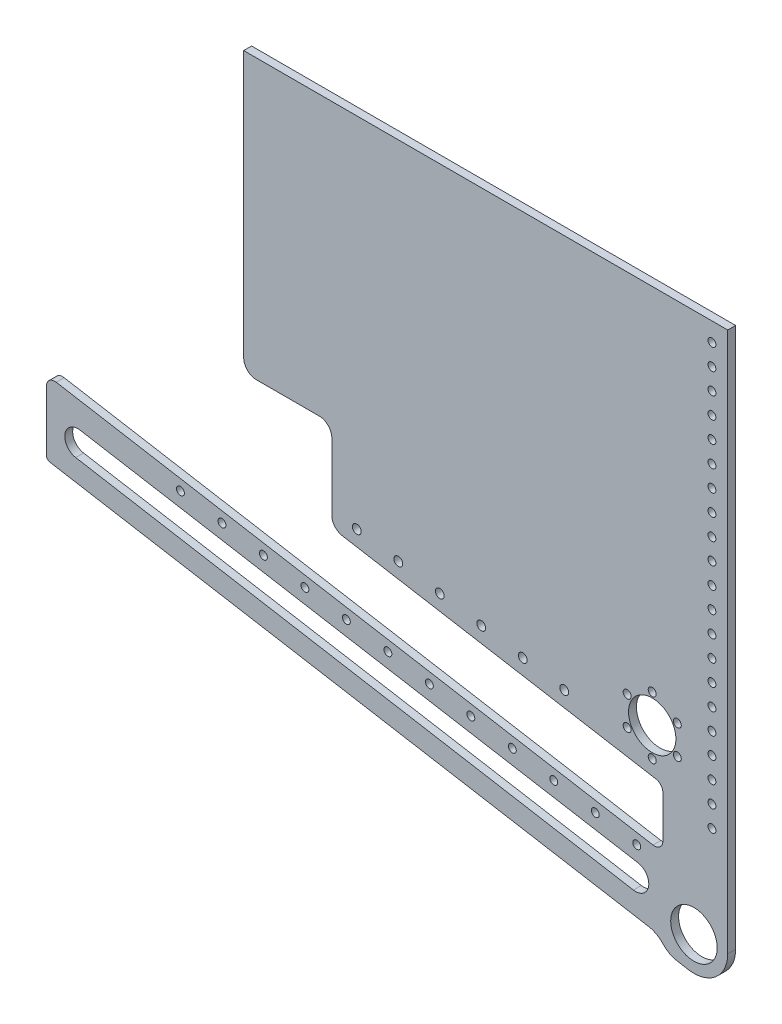
SolidWorks part; units mm, degrees
material "Polypropylene"
ref_plane "Front Plane" through (0, 0, 0) normal (0, 0, 1) x (1, 0, 0)
ref_plane "Top Plane" through (0, 0, 0) normal (0, 1, 0) x (1, 0, 0)
ref_plane "Right Plane" through (0, 0, 0) normal (1, 0, 0) x (0, 0, -1)
sketch "Sketch1" plane through (0, 0, 0) normal (0, 0, 1) x (1, 0, 0)
  line L0 (19.05, 0) -> (19.05, -76.2) construction
  line L1 (0, 19.05) -> (-57.15, 19.05) construction
  line L2 (19.05, -155.575) -> (168.9894, -155.575) construction
  line L3 (0, -95.25) -> (-57.15, -95.25) construction
  line L4 (-57.15, -95.25) -> (-57.15, 19.05) construction
  line L5 (168.9894, 7.239) -> (168.9894, -18.161) construction
  line L6 (168.9894, -18.161) -> (168.9894, -155.575) construction
  line L7 (168.9894, 7.239) -> (143.6189, 6.0141) construction
  line L8 (143.6189, 6.0141) -> (19.05, 0) construction
  line L9 (165.5424, -12.8509) -> (158.8645, -11.7052)
  line L10 (189.3729, 7.239) -> (189.3729, 131.5601)
  line L12 (197.5644, 110.4886) -> (197.5644, -33.1911) construction
  line L16 (-221.8076, 98.3842) -> (-221.8076, 62.1942)
  line L17 (133.7924, 19.9786) -> (-202.7576, 77.7234) construction
  line L18 (132.4501, 12.1554) -> (-204.0999, 69.9002)
  line L19 (135.1346, 27.8017) -> (-201.4154, 85.5465)
  line L20 (-215.8686, 103.3911) -> (107.3768, 47.929)
  line L23 (-219.6972, 59.6908) -> (141.5847, -2.2975)
  line L24 (179.8479, 131.5601) -> (179.8479, 118.8601) construction
  line L25 (179.8479, 118.8601) -> (189.3729, 118.8601) construction
  line L31 (107.3768, 47.929) -> (144.2855, 41.5963)
  line L32 (150.2246, 46.6031) -> (150.2246, 72.0031)
  line L38 (146.0036, 77.01) -> (-43.2183, 109.4764)
  line L40 (189.3729, 131.5601) -> (189.3729, 333.3075)
  line L42 (-102.7271, 172.6972) -> (-102.7271, 333.3075)
  line L43 (-102.7271, 333.3075) -> (189.3729, 333.3075)
  line L48 (-49.5497, 116.9867) -> (-49.5497, 157.4572)
  line L49 (-57.1697, 165.0772) -> (-95.1071, 165.0772)
  line L50 (-40.7554, 66.9026) -> (-34.4671, 117.3119) construction
  line L51 (34.3472, 54.0166) -> (40.7189, 104.4154) construction
  line L52 (-34.4671, 117.3119) -> (40.7189, 104.4154) construction
  arc A0 (19.05, 0) -> (0, 19.05) centre (0, 0) ccw construction
  arc A1 (19.05, -76.2) -> (0, -95.25) centre (0, -76.2) cw construction
  circle A2 centre (168.9894, 7.239) radius 14.0335
  arc A3 (168.9894, -18.161) -> (143.6189, 6.0141) centre (168.9894, 7.239) ccw construction
  arc A4 (165.5424, -12.8509) -> (189.3729, 7.239) centre (168.9894, 7.239) ccw
  arc A5 (132.4501, 12.1554) -> (135.1346, 27.8017) centre (133.7924, 19.9786) ccw
  arc A6 (-201.4154, 85.5465) -> (-204.0999, 69.9002) centre (-202.7576, 77.7234) ccw
  circle A8 centre (179.8479, 118.8601) radius 2.3813
  circle A9 centre (179.8479, 106.1601) radius 2.3813
  circle A10 centre (179.8479, 93.4601) radius 2.3813
  circle A11 centre (179.8479, 80.7601) radius 2.3813
  circle A12 centre (179.8479, 68.0601) radius 2.3813
  circle A15 centre (109.4497, 41.1306) radius 2.3813
  circle A16 centre (84.4155, 45.4259) radius 2.3812
  circle A17 centre (59.3813, 49.7212) radius 2.3813
  circle A18 centre (34.3472, 54.0166) radius 2.3813
  circle A19 centre (9.313, 58.3119) radius 2.3813
  circle A20 centre (-15.7212, 62.6072) radius 2.3812
  circle A21 centre (-40.7554, 66.9026) radius 2.3813
  circle A22 centre (-65.7896, 71.1979) radius 2.3813
  circle A23 centre (-90.8237, 75.4932) radius 2.3812
  circle A24 centre (-115.8579, 79.7886) radius 2.3813
  circle A25 centre (-140.8921, 84.0839) radius 2.3812
  circle A28 centre (134.4839, 36.8353) radius 2.3813
  arc A31 (-219.6972, 59.6908) -> (-221.8076, 62.1942) centre (-219.2676, 62.1942) cw
  arc A34 (158.8645, -11.7052) -> (150.2246, -7.0013) centre (161.4417, 3.3154) cw
  circle A39 centre (143.8098, 103.921) radius 21.9964 construction
  circle A40 centre (143.8098, 103.921) radius 14.2875
  circle A41 centre (143.8098, 103.921) radius 17.4625 construction
  circle A42 centre (143.8098, 121.3835) radius 2.413
  circle A43 centre (158.9328, 112.6523) radius 2.413
  circle A44 centre (158.9328, 95.1898) radius 2.413
  circle A45 centre (143.8098, 86.4585) radius 2.413
  circle A46 centre (128.6869, 95.1898) radius 2.413
  circle A47 centre (128.6869, 112.6523) radius 2.413
  arc A48 (141.5847, -2.2975) -> (150.2246, -7.0013) centre (139.0075, -17.318) cw
  arc A49 (144.2855, 41.5963) -> (150.2246, 46.6031) centre (145.1446, 46.6031) ccw
  arc A53 (-221.8076, 98.3842) -> (-215.8686, 103.3911) centre (-216.7276, 98.3842) cw
  arc A55 (150.2246, 72.0031) -> (146.0036, 77.01) centre (145.1446, 72.0031) ccw
  circle A57 centre (179.8479, 131.5601) radius 2.3813
  circle A58 centre (179.8479, 144.2601) radius 2.3813
  circle A59 centre (179.8479, 156.9601) radius 2.3812
  circle A60 centre (179.8479, 169.6601) radius 2.3813
  circle A61 centre (179.8479, 182.3601) radius 2.3813
  circle A62 centre (179.8479, 195.0601) radius 2.3813
  circle A63 centre (179.8479, 207.7601) radius 2.3813
  circle A64 centre (179.8479, 220.4601) radius 2.3812
  circle A65 centre (179.8479, 233.1601) radius 2.3813
  circle A66 centre (179.8479, 245.8601) radius 2.3813
  circle A67 centre (179.8479, 258.5601) radius 2.3813
  circle A68 centre (179.8479, 271.2601) radius 2.3813
  circle A69 centre (179.8479, 283.9601) radius 2.3812
  circle A70 centre (179.8479, 296.6601) radius 2.3812
  circle A71 centre (179.8479, 309.3601) radius 2.3813
  circle A72 centre (179.8479, 322.0601) radius 2.3813
  arc A79 (-43.2183, 109.4764) -> (-49.5497, 116.9867) centre (-41.9297, 116.9867) cw
  arc A80 (-102.7271, 172.6972) -> (-95.1071, 165.0772) centre (-95.1071, 172.6972) ccw
  arc A81 (-49.5497, 157.4572) -> (-57.1697, 165.0772) centre (-57.1697, 157.4572) ccw
  circle A84 centre (-9.4327, 113.0178) radius 2.667
  circle A86 centre (15.6017, 108.7237) radius 2.667
  circle A88 centre (40.636, 104.4296) radius 2.667
  circle A90 centre (65.6704, 100.1355) radius 2.667
  circle A92 centre (90.7048, 95.8414) radius 2.667
  circle A94 centre (-34.4671, 117.3119) radius 2.667
  point P24 (-34.4826, 48.851)
  point P51 (-221.8076, 53.6101)
  point P92 (143.8191, 3.8303)
  point P95 (150.6057, -10.2881)
  point P107 (-221.8076, 104.4101)
  point P118 (143.8098, 103.921)
  dimension "D1" = 19.05
  dimension "D4" = 19.05
  dimension "D6" = 28.067
  dimension "D7" = 50.8
  dimension "D10" = 6.35
  dimension "D13" = 28.575
  dimension "D15" = 7.9375
  dimension "D21" = 7.62
  dimension "D23" = 5
  dimension "D24" = 4.7625
  dimension "D25" = 5.08
  dimension "D26" = 2.54
  dimension "D27" = 15.24
  dimension "D28" = 12.7
  dimension "D30" = 5.08
  dimension "D31" = 43.9928
  dimension "D32" = 34.925
  dimension "D33" = 50.8
  dimension "D34" = 4.826
  dimension "D35" = 6
  dimension "D19" = 28.575
  dimension "D38" = 25.4
  dimension "D2" = 155.575
  dimension "D3" = 76.2
  dimension "D5" = 114.3
  dimension "D8" = 137.414
  dimension "D9" = 124.714
  dimension "D11" = 12.5
  dimension "D12" = 387.35
  dimension "D14" = 50.8
  dimension "D16" = 19.05
  dimension "D17" = 19.05
  dimension "D18" = 336.55
  dimension "D20" = 2
  dimension "D22" = 12.7
  dimension "D29" = 12.7
  dimension "D37" = 292.1
  dimension "D36" = 17
extrude "Boss-Extrude1" add sketch "Sketch1" along normal blind 4.7625
sketch "Sketch2" plane through (0, 0, 4.7625) normal (0, 0, 1) x (1, 0, 0)
  line L0 (-220.5687, 53.4619) -> (-220.7855, 56.0635)
  line L1 (-221.0377, 56.3386) -> (-222.0622, 56.5143)
  line L2 (-222.3916, 56.3391) -> (-223.4633, 53.9586)
  line L3 (-223.5225, 53.9043) -> (-223.5182, 53.9293) construction
  line L4 (-221.5499, 56.4265) -> (-222.0267, 53.6477) construction
  line L5 (-220.5266, 54.7046) -> (-223.0887, 55.1442) construction
  line L6 (158.8645, -11.7052) -> (165.5424, -12.8509) construction
  line L7 (-222.9409, 55.1189) -> (-223.1934, 53.6477) construction
  line L8 (-220.6744, 54.73) -> (-220.8601, 53.6477) construction
  line L11 (-220.5309, 53.391) -> (-223.5225, 53.9043)
  line L13 (-220.5266, 53.4161) -> (-220.056, 53.3353)
  line L14 (-220.056, 53.3353) -> (-220.0603, 53.3103)
  line L15 (-220.0603, 53.3103) -> (-220.5309, 53.391)
  line L16 (-220.5309, 53.391) -> (-220.5266, 53.4161) construction
  line L17 (-223.9889, 54.0101) -> (-223.9931, 53.9851)
  line L18 (-223.9931, 53.9851) -> (-223.5225, 53.9043)
  line L19 (-223.5182, 53.9293) -> (-223.9889, 54.0101)
  line L21 (-221.8076, 98.3842) -> (-221.8076, 62.1942) construction
  arc A0 (-222.0622, 56.5143) -> (-222.3916, 56.3391) centre (-222.1137, 56.2139) ccw
  arc A1 (-220.7855, 56.0635) -> (-221.0377, 56.3386) centre (-221.0892, 56.0382) ccw
  arc A2 (-223.5182, 53.9293) -> (-223.4633, 53.9586) centre (-223.5096, 53.9794) ccw
  arc A3 (-220.5687, 53.4619) -> (-220.5266, 53.4161) centre (-220.518, 53.4661) ccw
  point P6 (-221.8076, 54.9244)
  dimension "D1" = 0.0254
  dimension "Root_fillet" = 0.3048
  dimension "Break_rad" = 0.0508
  dimension "Gap_width" = 2.2997
  dimension "Dedendum" = 1.524
  dimension "Addendum_plus" = 1.2954
  dimension "Pressure_angle" = 14.5
  dimension "D2" = 0.4775
